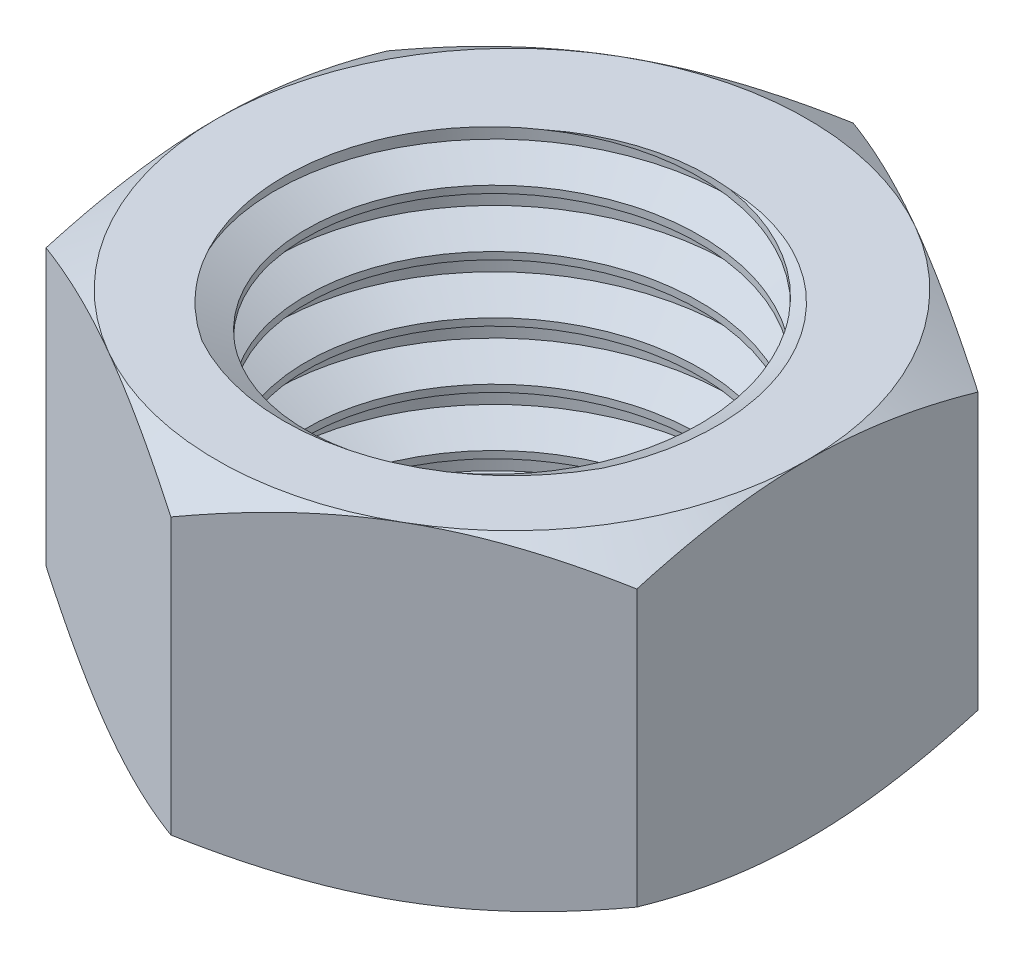
SolidWorks part; units mm, degrees
material "Plain Carbon Steel"
ref_plane "Front Plane" through (0, 0, 0) normal (0, 0, 1) x (1, 0, 0)
ref_plane "Top Plane" through (0, 0, 0) normal (0, 1, 0) x (1, 0, 0)
ref_plane "Right Plane" through (0, 0, 0) normal (1, 0, 0) x (0, 0, -1)
sketch "Sketch1" plane through (0, 0, 0) normal (0, 1, 0) x (1, 0, 0)
  line L1 (0, 10.3923) -> (-9, 5.1962)
  line L2 (-9, 5.1962) -> (-9, -5.1962)
  line L3 (-9, -5.1962) -> (0, -10.3923)
  line L4 (0, -10.3923) -> (9, -5.1962)
  line L5 (9, -5.1962) -> (9, 5.1962)
  line L6 (9, 5.1962) -> (0, 10.3923)
  circle A0 centre (0, 0) radius 9 construction
  circle A1 centre (0, 0) radius 1.5
  dimension "D2" = 3
  dimension "D1" = 18
extrude "Boss-Extrude2" add sketch "Sketch1" along normal blind 10 contours L4 L5 L6 L1 L2 L3
sketch "Sketch18" plane through (0, 10, 0) normal (0, 1, 0) x (1, 0, 0)
  circle A0 centre (0, 0) radius 6
  dimension "D1" = 12
extrude "Cut-Extrude1" cut sketch "Sketch18" against normal through all
sketch "Sketch20" plane through (0, 0, 0) normal (0, -1, 0) x (1, 0, 0)
  line L0 (0, 10.3923) -> (9, 5.1962) construction
  circle A0 centre (0, 0) radius 9
extrude "Cut-Extrude4" cut sketch "Sketch20" against normal blind 10.8 draft 60 flip side to cut contours A0
sketch "Sketch21" plane through (0, 10, 0) normal (0, 1, 0) x (1, 0, 0)
  line L0 (9, 5.1962) -> (0, 10.3923) construction
  circle A0 centre (0, 0) radius 9
extrude "Cut-Extrude5" cut sketch "Sketch21" against normal blind 10.8 draft 60 flip side to cut
thread "Thread3" pitch 1.75 method cut trim with start face yes trim with end face yes profile "Thread Profile3" start angle 0, offset 2, length 12, pitch 1.75, diameter 12
ref_plane "Plane3" through (-6, 12, 0) normal (0, 0, -1) x (1, 0, 0)
sketch "Thread Profile3" plane through (-6, 12, 0) normal (0, 0, -1) x (1, 0, 0)
  line L0 (0, 0) -> (0, 1.75) construction
  line L11 (0, 0) -> (0, 1.5312)
  line L12 (0, 1.5312) -> (-0.9472, 0.9844)
  line L13 (-0.9472, 0.9844) -> (-0.9472, 0.5469)
  line L15 (-0.9472, 0.5469) -> (0, 0)
  line L17 (-0.9472, 0.7656) -> (0, 0.7656) construction
  point P2 (0, 0)
  dimension "Pitch" = 1.75
  dimension "Profile_Angle" = 60
  dimension "Profile_Land" = 0.4375
  dimension "Profile_Height" = 0.9472
sketch "Sketch26" plane through (0, 10, 0) normal (0, 1, 0) x (1, 0, 0)
  circle A0 centre (0, 0) radius 1.5
  dimension "D1" = 3
